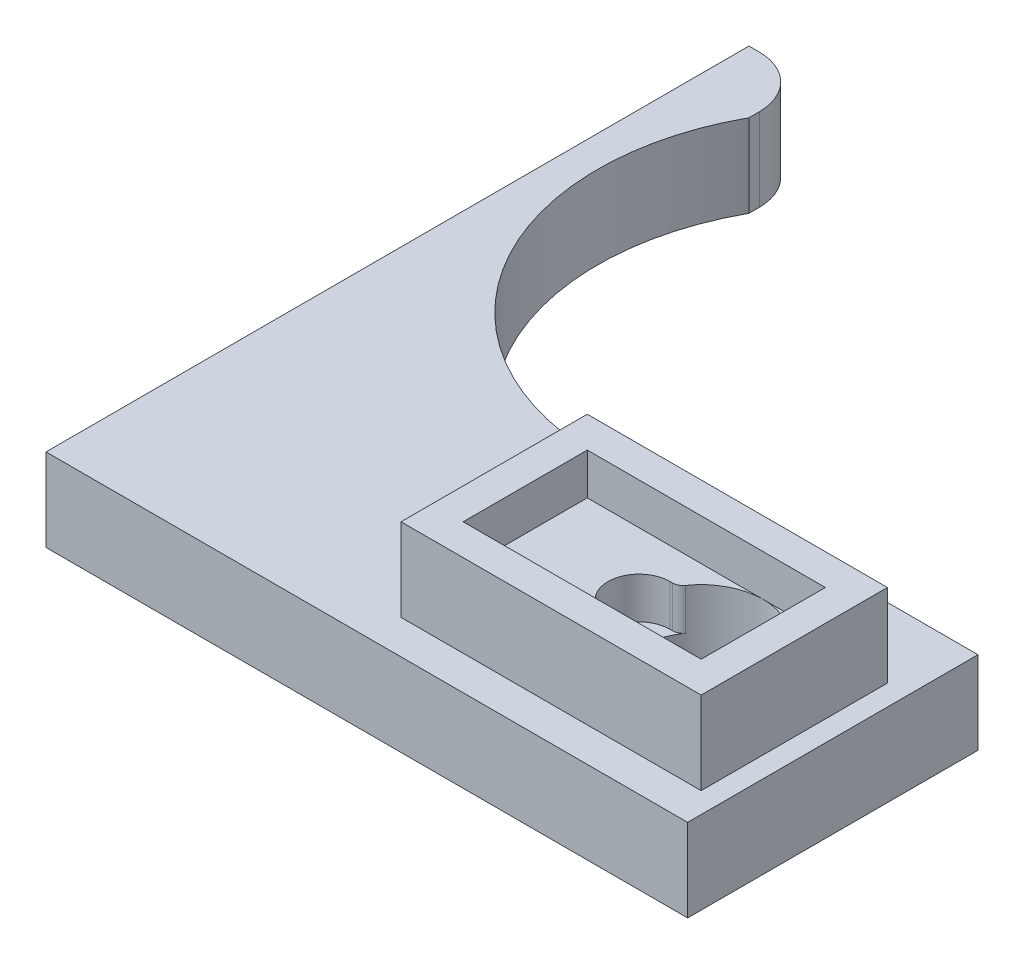
SolidWorks part; units mm, degrees
ref_plane "Plan de face" through (0, 0, 0) normal (0, 0, 1) x (1, 0, 0)
ref_plane "Plan de dessus" through (0, 0, 0) normal (0, 1, 0) x (1, 0, 0)
ref_plane "Plan de droite" through (0, 0, 0) normal (1, 0, 0) x (0, 0, -1)
sketch "Esquisse1" plane through (0, 0, 0) normal (0, 1, 0) x (1, 0, 0)
  line L1 (0, 0) -> (6, 0)
  line L2 (0, 0) -> (0, 67.9235)
  line L3 (0, 67.9235) -> (1, 67.9235)
  line L4 (6, 0) -> (6, 67.9235) construction
  line L5 (36, 0) -> (6, 0)
  line L6 (6, 61.9235) -> (6, 62.9235)
  line L7 (52, 50.3046) -> (52, 0) construction
  line L8 (36, 28.056) -> (62, 28.056)
  line L10 (36, 0) -> (62, 0)
  line L11 (62, 28.056) -> (62, 0)
  line L12 (36, 28.056) -> (36, 0) construction
  line L13 (52, 12.3046) -> (51, 12.3046) construction
  arc A0 (6, 61.9235) -> (36, 28.056) centre (27, 50.3046) ccw
  circle A1 centre (27, 50.3046) radius 25 construction
  arc A2 (1, 67.9235) -> (6, 62.9235) centre (1, 62.9235) cw
  circle A3 centre (51, 12.3046) radius 6
  point P13 (0, 0)
  dimension "D1" = 24
  dimension "D3" = 50
  dimension "D7" = 5
  dimension "D9" = 12
  dimension "D2" = 21
  dimension "D4" = 30
  dimension "D5" = 6
  dimension "D6" = 6
  dimension "D8" = 1
  dimension "D10" = 38
  dimension "D11" = 62
extrude "Boss.-Extru.1" add sketch "Esquisse1" along normal blind 8
sketch "Esquisse2" plane through (0, 8, 0) normal (0, 1, 0) x (1, 0, 0)
  line L0 (51, 12.3046) -> (45, 12.3046) construction
  line L1 (45, 15.3046) -> (45.2554, 15.3046)
  line L2 (45, 9.3046) -> (45.2554, 9.3046)
  line L8 (31, 21.3046) -> (60, 21.3046)
  line L9 (31, 21.3046) -> (31, 3.3046)
  line L10 (31, 3.3046) -> (60, 3.3046)
  line L11 (60, 21.3046) -> (60, 3.3046)
  circle A0 centre (51, 12.3046) radius 6 construction
  circle A1 centre (45, 12.3046) radius 3 construction
  arc A2 (46.0761, 15.7332) -> (46.0761, 8.876) centre (51, 12.3046) cw
  arc A3 (45, 15.3046) -> (45, 9.3046) centre (45, 12.3046) ccw
  arc A4 (45.2554, 9.3046) -> (46.0761, 8.876) centre (45.2554, 8.3046) cw
  arc A5 (45.2554, 15.3046) -> (46.0761, 15.7332) centre (45.2554, 16.3046) ccw
  point P12 (57, 12.3046)
  point P15 (45.8038, 9.3046)
  point P18 (45.8038, 15.3046)
  point P27 (60, 12.3046)
  dimension "D1" = 12
  dimension "D2" = 6
  dimension "D4" = 1
  dimension "D3" = 6
  dimension "D5" = 9
  dimension "D7" = 18
  dimension "D8" = 29
extrude "Boss.-Extru.2" add sketch "Esquisse2" along normal blind 4 contours L9 L8 L11 L10 | A3 L2 A4 A2 A5 L1
sketch "Esquisse3" plane through (0, 12, 0) normal (0, 1, 0) x (1, 0, 0)
  line L1 (34, 18.3046) -> (57, 18.3046)
  line L2 (34, 18.3046) -> (34, 6.3046)
  line L3 (34, 6.3046) -> (57, 6.3046)
  line L4 (57, 18.3046) -> (57, 6.3046)
  line L5 (31, 21.3046) -> (60, 21.3046)
  line L6 (31, 21.3046) -> (31, 3.3046)
  line L7 (31, 3.3046) -> (60, 3.3046)
  line L8 (60, 21.3046) -> (60, 3.3046)
  arc A0 (46.0761, 8.876) -> (46.0761, 15.7332) centre (51, 12.3046) ccw construction
  dimension "D1" = 12
  dimension "D2" = 23
extrude "Boss.-Extru.3" add sketch "Esquisse3" along normal blind 4
sketch "Esquisse4" plane through (0, 0, 0) normal (0, -1, 0) x (1, 0, 0)
  line L0 (62, -28.056) -> (36, -28.056) construction
  line L1 (47.7, -17.056) -> (54.3, -17.056)
  line L3 (47.7, -28.056) -> (54.3, -28.056)
  line L5 (51, -12.3046) -> (51, -17.056) construction
  line L6 (51, -12.3046) -> (52.0099, -17.056) construction
  line L7 (55.1937, -16.1623) -> (57.7218, -28.056)
  line L8 (54.3, -17.056) -> (55.1937, -16.1623)
  line L9 (54.3, -28.056) -> (57.7218, -28.056)
  line L10 (54.3, -17.056) -> (54.3, -28.056) construction
  line L11 (46.8063, -16.1623) -> (44.2782, -28.056)
  line L12 (46.8063, -16.1623) -> (47.7, -17.056)
  line L13 (47.7, -17.056) -> (47.7, -28.056) construction
  line L14 (44.2782, -28.056) -> (47.7, -28.056)
  point P12 (51, -17.056)
  dimension "D1" = 12
  dimension "D2" = 3.3
  dimension "D3" = 6.6
  dimension "D4" = 11
  dimension "D5" = 135
extrude "Enlèv. mat.-Extru.1" cut sketch "Esquisse4" against normal blind 4
